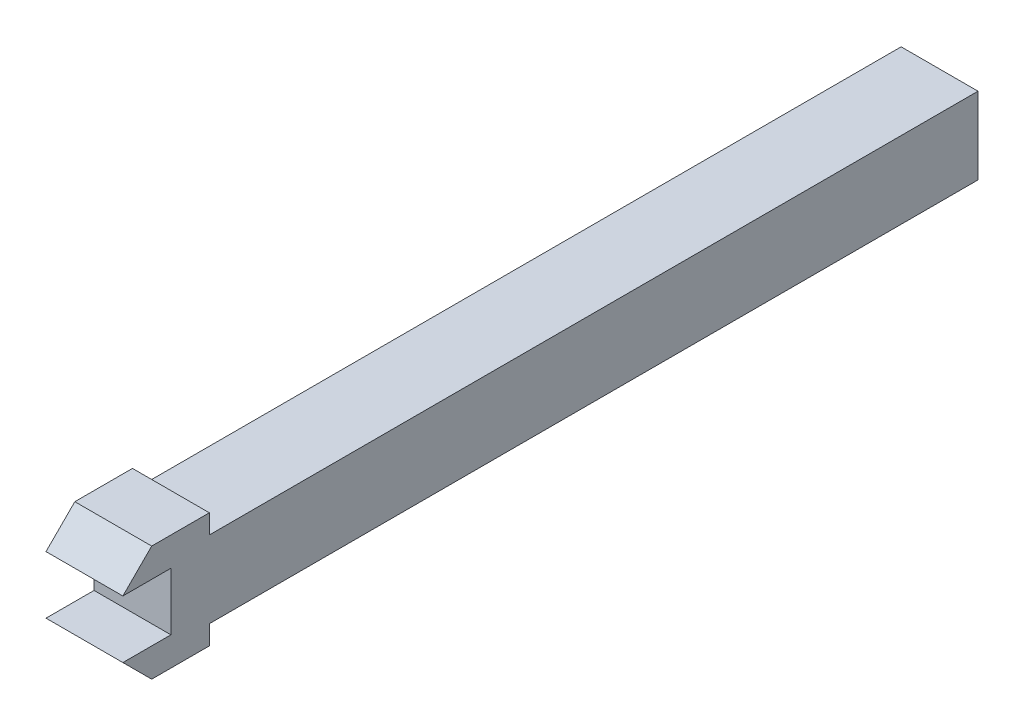
SolidWorks part; units mm, degrees
ref_plane "Front Plane" through (0, 0, 0) normal (0, 0, 1) x (1, 0, 0)
ref_plane "Top Plane" through (0, 0, 0) normal (0, 1, 0) x (1, 0, 0)
ref_plane "Right Plane" through (0, 0, 0) normal (1, 0, 0) x (0, 0, -1)
sketch "Sketch1" plane through (0, 0, 0) normal (0, 0, 1) x (1, 0, 0)
  line L1 (-10, -10) -> (10, -10)
  line L2 (-10, -10) -> (-10, 10)
  line L3 (-10, 10) -> (10, 10)
  line L4 (10, -10) -> (10, 10)
  line L5 (-10, -10) -> (10, 10) construction
  line L6 (-10, 10) -> (10, -10) construction
  point P0 (0, 0)
  dimension "D1" = 20
  dimension "D2" = 20
extrude "Boss-Extrude1" add sketch "Sketch1" along normal blind 200
sketch "Sketch2" plane through (0, 0, 200) normal (0, 0, 1) x (1, 0, 0)
  line L1 (-10, -15) -> (10, -15)
  line L2 (-10, -15) -> (-10, 15)
  line L3 (-10, 15) -> (10, 15)
  line L4 (10, -15) -> (10, 15)
  line L5 (-10, -15) -> (10, 15) construction
  line L6 (-10, 15) -> (10, -15) construction
  point P0 (0, 0)
  dimension "D1" = 20
  dimension "D2" = 30
extrude "Boss-Extrude2" add sketch "Sketch2" along normal blind 25
sketch "Sketch3" plane through (0, 0, 225) normal (0, 0, 1) x (1, 0, 0)
  line L1 (-10, -7.5) -> (10, -7.5)
  line L2 (-10, -7.5) -> (-10, 7.5)
  line L3 (-10, 7.5) -> (10, 7.5)
  line L4 (10, -7.5) -> (10, 7.5)
  line L5 (-10, -7.5) -> (10, 7.5) construction
  line L6 (-10, 7.5) -> (10, -7.5) construction
  point P0 (0, 0)
  dimension "D1" = 20
  dimension "D2" = 15
extrude "Cut-Extrude1" cut sketch "Sketch3" against normal blind 15
chamfer "Chamfer1" distance 10 angle 45 1 edges at (0, 15, 225)
chamfer "Chamfer3" distance 10 angle 45 1 edges at (0, -15, 225)
